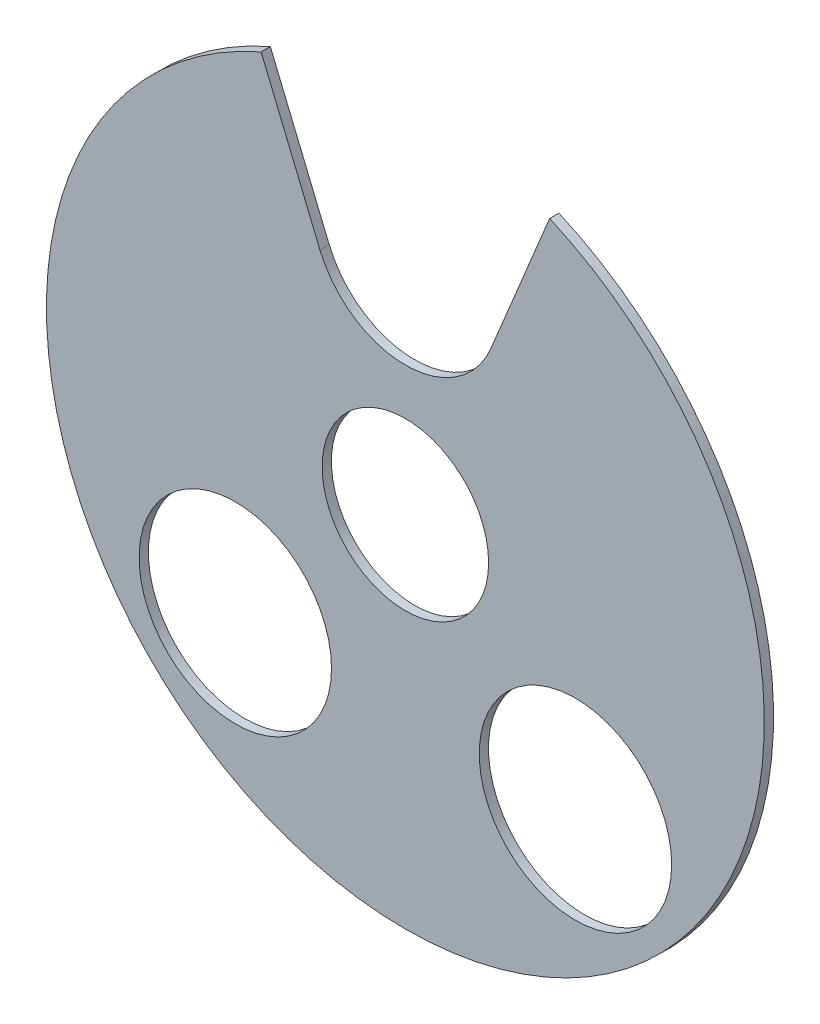
SolidWorks part; units mm, degrees
ref_plane "Front Plane" through (0, 0, 0) normal (0, 0, 1) x (1, 0, 0)
ref_plane "Top Plane" through (0, 0, 0) normal (0, 1, 0) x (1, 0, 0)
ref_plane "Right Plane" through (0, 0, 0) normal (1, 0, 0) x (0, 0, -1)
sketch "Esquisse1" plane through (0, 0, 0) normal (0, 0, 1) x (1, 0, 0)
  circle A0 centre (0, 0) radius 97
  circle A1 centre (0, 0) radius 22.5
  dimension "D1" = 194
  dimension "D2" = 45
extrude "Main" add sketch "Esquisse1" along normal blind 2.5
sketch "Esquisse2" plane through (0, 0, 2.5) normal (0, 0, 1) x (1, 0, 0)
  line L0 (-23.097, 50.4329) -> (-38.9959, 88.8162)
  line L1 (23.097, 50.4329) -> (38.9959, 88.8162)
  line L2 (0, 0) -> (0, -112.8607) construction
  line L3 (-45.9619, -45.9619) -> (0, 0) construction
  arc A0 (-23.097, 50.4329) -> (23.097, 50.4329) centre (0, 60) ccw
  circle A1 centre (0, 0) radius 97 construction
  circle A2 centre (-45.9619, -45.9619) radius 26
  circle A3 centre (45.9619, -45.9619) radius 26
  arc A4 (-38.9959, 88.8162) -> (38.9959, 88.8162) centre (0, 0) cw
  point P12 (14.7635, 66.4949)
  point P16 (0, 0)
  point P17 (38.0312, 89.2335)
  dimension "D2" = 25
  dimension "D4" = 52
  dimension "D1" = 45
  dimension "D3" = 60
  dimension "D5" = 45
  dimension "D6" = 90
  dimension "D7" = 65
extrude "Holes" cut sketch "Esquisse2" against normal through all and the other way through all
